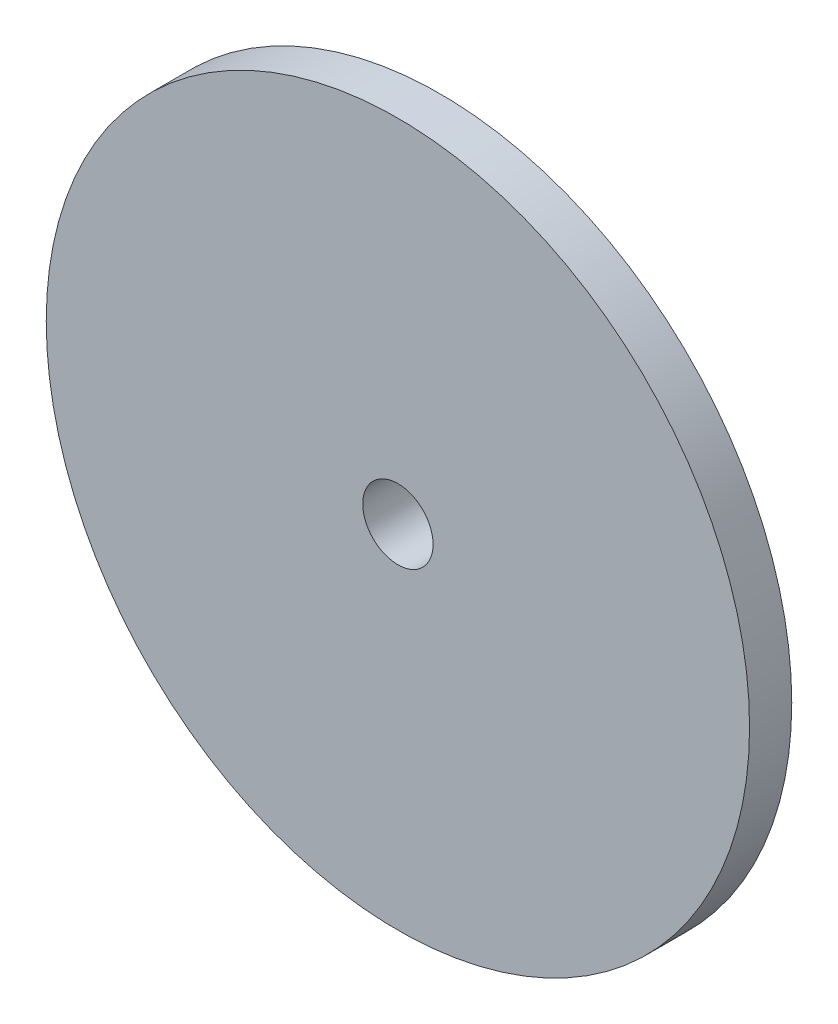
SolidWorks part; units mm, degrees
ref_plane "Front Plane" through (0, 0, 0) normal (0, 0, 1) x (1, 0, 0)
ref_plane "Top Plane" through (0, 0, 0) normal (0, 1, 0) x (1, 0, 0)
ref_plane "Right Plane" through (0, 0, 0) normal (1, 0, 0) x (0, 0, -1)
sketch "Sketch1" plane through (0, 0, 0) normal (0, 0, 1) x (1, 0, 0)
  circle A2 centre (-27.2624, 0) radius 12.5
  circle A3 centre (-27.2624, 0) radius 1.25
  circle A5 centre (-27.2624, 0) radius 6
  dimension "D1" = 12
  dimension "D2" = 25
extrude "Boss-Extrude1" add sketch "Sketch1" against normal blind 0.4 contours A5 A3 region at (-33.0927, 0, 0)
extrude "Boss-Extrude2" add sketch "Sketch1<3>" along normal blind 1.5 contours A2 A5 | A5 A3 region at (-39.4088, 0, 0) region at (-33.0927, 0, 0)
sketch "Sketch1<3>" plane through (0, 0, 0) normal (0, 0, 1) x (1, 0, 0) same geometry as "Sketch1"
